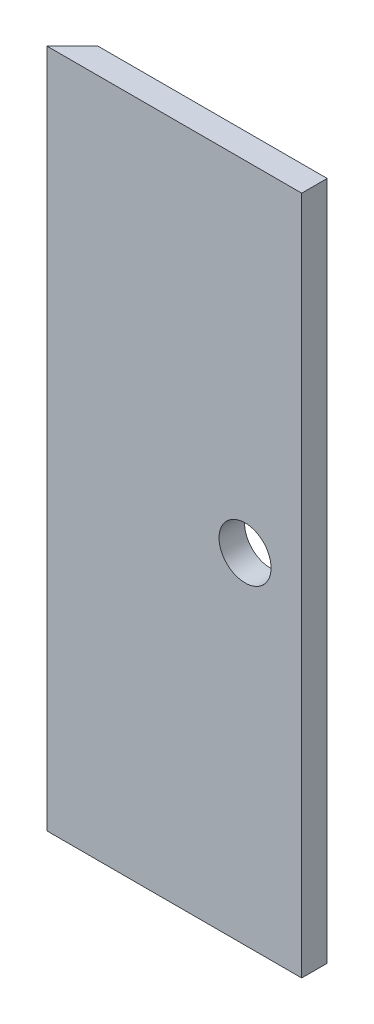
SolidWorks part; units mm, degrees
ref_plane "Front Plane" through (0, 0, 0) normal (0, 0, 1) x (1, 0, 0)
ref_plane "Top Plane" through (0, 0, 0) normal (0, 1, 0) x (1, 0, 0)
ref_plane "Right Plane" through (0, 0, 0) normal (1, 0, 0) x (0, 0, -1)
sketch "Sketch1" plane through (0, 0, 0) normal (0, 0, 1) x (1, 0, 0)
  line L0 (180, 240) -> (0, 240) construction
  line L1 (0, 0) -> (180, 0)
  line L2 (0, 0) -> (0, 480)
  line L3 (0, 480) -> (180, 480)
  line L4 (180, 0) -> (180, 480)
  circle A1 centre (140, 240) radius 18.3687
  dimension "D1" = 140
  dimension "D2" = 180
  dimension "D3" = 480
extrude "Boss-Extrude1" add sketch "Sketch1" along normal blind 18
chamfer "Chamfer1" distance 18 angle 45 1 edges at (0, 240, 0)
